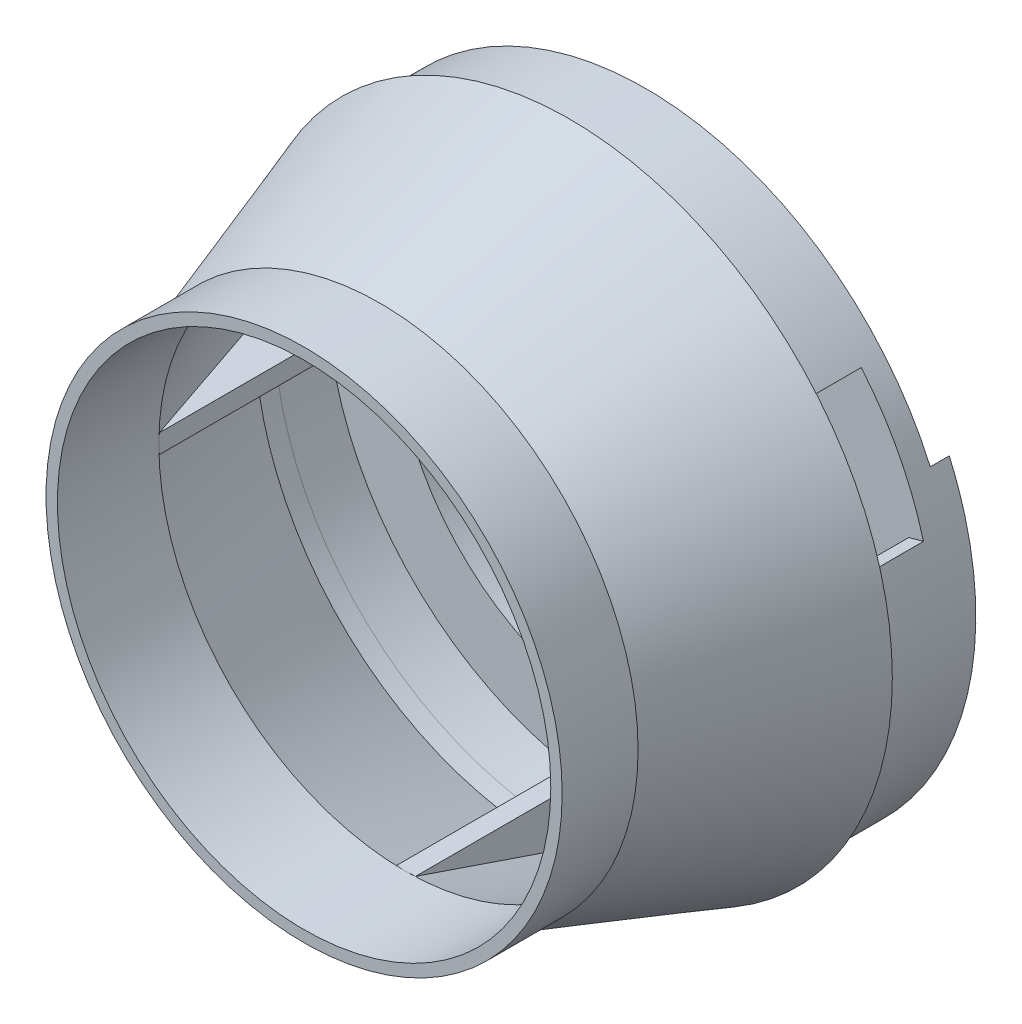
SolidWorks part; units mm, degrees
material "Polyetheretherketone (PEEK)"
ref_plane "Front Plane" through (0, 0, 0) normal (0, 0, 1) x (1, 0, 0)
ref_plane "Top Plane" through (0, 0, 0) normal (0, 1, 0) x (1, 0, 0)
ref_plane "Right Plane" through (0, 0, 0) normal (1, 0, 0) x (0, 0, -1)
sketch "Sketch10" plane through (0, 0, 0) normal (0, 1, 0) x (1, 0, 0)
  line L9 (68, 0) -> (85, 50)
  line L10 (65, 6.7091) -> (65, -20)
  line L11 (65, -20) -> (68, -20)
  line L12 (68, -20) -> (68, 0)
  line L13 (85, 50) -> (82, 50)
  line L16 (0, 0) -> (0, 90.5218) construction
  line L19 (65, 6.7091) -> (78.0189, 45)
  line L20 (63.2661, 1.6095) -> (80.2661, 51.6095) construction
  line L21 (-55, 0) -> (55, 0) construction
  line L22 (0, -55) -> (0, 55) construction
  line L25 (82, 50) -> (82, 70)
  line L26 (82, 70) -> (60, 70)
  line L27 (78, 50) -> (78, 64)
  line L28 (78, 64) -> (60, 64)
  line L29 (60, 64) -> (60, 70)
  line L31 (78, 50) -> (78.0189, 45)
  dimension "D1" = 50
  dimension "D2" = 20
  dimension "D3" = 65
  dimension "D4" = 85
  dimension "D5" = 68
  dimension "D7" = 5
  dimension "D8" = 6
  dimension "D9" = 82
  dimension "D10" = 20
  dimension "D11" = 4
  dimension "D12" = 60
revolve "Revolve2" add sketch "Sketch10" angle 360 about L16
sketch "Sketch37" plane through (0, 0, 0) normal (0, 1, 0) x (1, 0, 0)
  line L0 (-65, 6.7091) -> (-65, 70)
  line L4 (82, 70) -> (-82, 70) construction
  line L5 (-65, 70) -> (-78, 64)
  line L6 (-78, 64) -> (-78.0189, 45)
  line L7 (-78.0189, 45) -> (-65, 6.7091)
sketch "Sketch19" plane through (0, 0, -50) normal (0, 0, -1) x (-1, 0, 0)
  line L0 (-75.3422, 20.1879) -> (-79.2059, 21.2232)
  line L7 (-59.7515, 50.1374) -> (-62.8156, 52.7086)
  line L8 (0, 52.25) -> (0, -52.25) construction
  line L9 (59.7515, 50.1374) -> (62.8156, 52.7086)
  line L10 (75.3422, 20.1879) -> (79.2059, 21.2232)
  line L11 (0, 0) -> (-59.7515, 50.1374) construction
  line L12 (0, 0) -> (59.7515, 50.1374) construction
  line L13 (0, 0) -> (75.3422, 20.1879) construction
  line L14 (0, 0) -> (-75.3422, 20.1879) construction
  arc A0 (62.8156, 52.7086) -> (79.2059, 21.2232) centre (0, 0) cw
  arc A3 (75.3422, 20.1879) -> (59.7515, 50.1374) centre (0, 0) ccw
  circle A4 centre (0, 0) radius 82 construction
  circle A5 centre (0, 0) radius 82 construction
  arc A6 (-62.8156, 52.7086) -> (-79.2059, 21.2232) centre (0, 0) ccw
  arc A8 (-59.7515, 50.1374) -> (-75.3422, 20.1879) centre (0, 0) ccw
  circle A9 centre (0, 0) radius 78 construction
  dimension "D1" = 50
  dimension "D2" = 75
extrude "Cut-Extrude7" cut sketch "Sketch19" along normal up to surface (14 mm away) up to face at (78, 0, -64)
sketch "Sketch29" plane through (0, 0, -70) normal (0, 0, -1) x (-1, 0, 0)
  line L9 (-75, 0) -> (-75, 33.1512)
  line L10 (0, 49.5) -> (0, -49.5) construction
  line L11 (75, 0) -> (75, 33.1512)
  arc A0 (-75, 33.1512) -> (75, 33.1512) centre (0, 0) ccw
  arc A2 (-75, 0) -> (75, 0) centre (0, 0) ccw
  circle A3 centre (0, 0) radius 82 construction
  dimension "D3" = 150
extrude "Boss-Extrude10" add sketch "Sketch29" along normal blind 5 contours A0 L11 A2 L9
extrude "Boss-Extrude11" add sketch "Sketch37" along normal blind 2.5 and the other way blind 2.5 contours L0 L5 L6 L7
pattern_circular "CirPattern1" count 4 over 360 about axis through (0, 0, 20) along (0, 0, 1) of "Boss-Extrude11"
